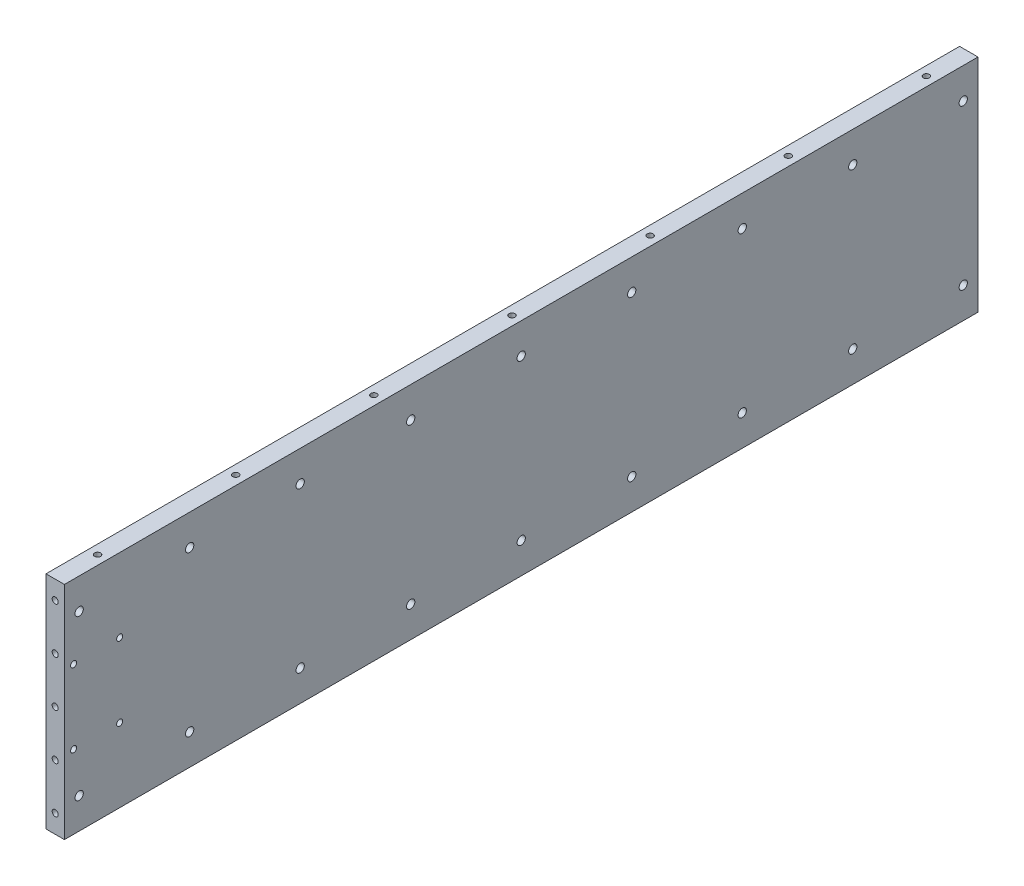
SolidWorks part; units mm, degrees
ref_plane "Front Plane" through (0, 0, 0) normal (0, 0, 1) x (1, 0, 0)
ref_plane "Top Plane" through (0, 0, 0) normal (0, 1, 0) x (1, 0, 0)
ref_plane "Right Plane" through (0, 0, 0) normal (1, 0, 0) x (0, 0, -1)
sketch "Sketch2" plane through (0, 0, 0) normal (0, 0, 1) x (1, 0, 0)
  line L0 (-10, 0) -> (0, 0)
  line L3 (0, 0) -> (0, -120)
  line L4 (0, -120) -> (-10, -120)
  line L5 (-10, -120) -> (-10, 0)
  dimension "D1" = 120
  dimension "D2" = 10
extrude "Boss-Extrude1" add sketch "Sketch2" along normal blind 496
sketch "Sketch3" plane through (0, 0, 496) normal (0, 0, 1) x (1, 0, 0)
  line L0 (-5, 0) -> (-5, -120) construction
  line L1 (0, 0) -> (-10, 0) construction
  line L2 (-10, -120) -> (0, -120) construction
  line L3 (-10, -60) -> (0, -60) construction
  line L4 (-10, 0) -> (-10, -120) construction
  line L5 (0, -120) -> (0, 0) construction
  point P12 (-5, -60)
  point P13 (-5, -110)
  point P14 (-5, -35)
  point P15 (-5, -10)
  point P16 (-5, -85)
  dimension "D1" = 3
hole_wizard "M4 Tapped Hole1" positions "3DSketch1" profile "Sketch4" tap size "M4" standard "ISO"
sketch3d "3DSketch1"
  point P0 (-5, -10, 496)
  point P3 (-5, -35, 496)
  point P6 (-5, -60, 496)
  point P9 (-5, -85, 496)
  point P12 (-5, -110, 496)
sketch "Sketch4" plane through (-5, -10, 496) normal (1, 0, 0) x (0, -1, 0)
  line L0 (0, 0) -> (0, 15.0914)
  line L1 (0, 15.0914) -> (1.65, 14.1)
  line L2 (1.65, 14.1) -> (1.65, 0)
  line L5 (1.65, 0) -> (0, 0)
  line L10 (0, 15.0914) -> (-1.65, 14.1) construction
  line L11 (0, -6.35) -> (0, 107.95) construction
  dimension "Tap Drill Dia." = 3.3
  dimension "Tap Drill Depth" = 14.1
  dimension "Drill Angle" = 118
sketch "Sketch5" plane through (0, 0, 0) normal (0, 0, -1) x (-1, 0, 0)
  line L0 (5, 0) -> (5, -120) construction
  line L1 (0, 0) -> (10, 0) construction
  line L2 (10, -120) -> (0, -120) construction
  line L3 (10, -60) -> (0, -60) construction
  point P10 (5, -60)
  point P11 (5, -85)
  point P12 (5, -35)
  point P13 (5, -10)
  point P14 (5, -110)
  dimension "D1" = 3
hole_wizard "M4 Tapped Hole2" positions "3DSketch2" profile "Sketch6" tap size "M4" standard "ISO"
sketch3d "3DSketch2"
  point P0 (-5, -10, 0)
  point P3 (-5, -35, 0)
  point P6 (-5, -60, 0)
  point P9 (-5, -85, 0)
  point P12 (-5, -110, 0)
sketch "Sketch6" plane through (-5, -10, 0) normal (1, 0, 0) x (0, 1, 0)
  line L0 (0, 0) -> (0, 15.0914)
  line L1 (0, 15.0914) -> (1.65, 14.1)
  line L2 (1.65, 14.1) -> (1.65, 0)
  line L5 (1.65, 0) -> (0, 0)
  line L10 (0, 15.0914) -> (-1.65, 14.1) construction
  line L11 (0, -6.35) -> (0, 107.95) construction
  dimension "Tap Drill Dia." = 3.3
  dimension "Tap Drill Depth" = 14.1
  dimension "Drill Angle" = 118
sketch "Sketch7" plane through (0, 0, 0) normal (1, 0, 0) x (0, 0, -1)
  line L0 (-496, -60) -> (0, -60) construction
  line L1 (0, 0) -> (0, -120) construction
  line L2 (-496, -16.7) -> (0, -16.7) construction
  line L3 (-496, 0) -> (-496, -120) construction
  line L4 (-496, 0) -> (0, 0) construction
  point P11 (-488, -16.7)
  point P12 (-8, -103.3)
  point P13 (-428, -16.7)
  point P14 (-368, -16.7)
  point P15 (-308, -16.7)
  point P16 (-248, -16.7)
  point P17 (-188, -16.7)
  point P18 (-128, -16.7)
  point P19 (-68, -16.7)
  point P20 (-8, -16.7)
  point P21 (-68, -103.3)
  point P22 (-128, -103.3)
  point P23 (-188, -103.3)
  point P24 (-248, -103.3)
  point P25 (-308, -103.3)
  point P26 (-368, -103.3)
  point P27 (-428, -103.3)
  point P28 (-488, -103.3)
  dimension "D1" = 16.7
  dimension "D2" = 8
  dimension "D3" = 9
hole_wizard "Ø4.5 (4.5) Diameter Hole1" positions "3DSketch3" profile "Sketch8" hole size "Ø4.5" standard "ISO" end condition through all
sketch3d "3DSketch3"
  point P0 (0, -16.7, 488)
  point P3 (0, -16.7, 428)
  point P6 (0, -16.7, 368)
  point P9 (0, -16.7, 308)
  point P12 (0, -16.7, 248)
  point P15 (0, -16.7, 188)
  point P18 (0, -16.7, 128)
  point P21 (0, -16.7, 68)
  point P24 (0, -16.7, 8)
  point P27 (0, -103.3, 8)
  point P30 (0, -103.3, 68)
  point P33 (0, -103.3, 128)
  point P36 (0, -103.3, 188)
  point P39 (0, -103.3, 248)
  point P42 (0, -103.3, 308)
  point P45 (0, -103.3, 368)
  point P48 (0, -103.3, 428)
  point P51 (0, -103.3, 488)
sketch "Sketch8" plane through (0, -16.7, 488) normal (0, 1, 0) x (0, 0, -1)
  line L0 (0, 0) -> (0, 10)
  line L1 (0, 10) -> (2.25, 10)
  line L2 (2.25, 10) -> (2.25, 0)
  line L5 (2.25, 0) -> (0, 0)
  line L11 (0, -6.35) -> (0, 107.95) construction
  dimension "Thru Hole Dia." = 4.5
  dimension "Thru Hole Depth" = 10
sketch "Sketch9" plane through (0, 0, 0) normal (1, 0, 0) x (0, 0, -1)
  line L0 (-495.4373, -40) -> (-462.5242, -40) construction
  line L1 (-504.5233, -37.9) -> (-462.0233, -37.9) construction
  line L2 (-504.5233, -42.1) -> (-462.0233, -42.1) construction
  line L4 (-462.5242, -80) -> (-495.4373, -80) construction
  line L5 (-504.5233, -77.9) -> (-462.0233, -77.9) construction
  line L6 (-504.5233, -82.1) -> (-462.0233, -82.1) construction
  line L7 (-496, -258) -> (-496, 0) construction
  line L10 (-496, 0) -> (-496, -120) construction
  point P12 (-466, -40)
  point P13 (-491, -40)
  point P18 (-491, -80)
  point P19 (-466, -80)
  dimension "D1" = 5
  dimension "D2" = 30
hole_wizard "M4 Tapped Hole3" positions "3DSketch5" profile "Sketch11" tap size "M4" standard "ISO" end condition through all
sketch3d "3DSketch5"
  point P0 (0, -40, 491)
  point P3 (0, -40, 466)
  point P6 (0, -80, 491)
  point P9 (0, -80, 466)
sketch "Sketch11" plane through (0, -40, 491) normal (0, 1, 0) x (0, 0, -1)
  line L0 (0, 0) -> (0, 10)
  line L1 (0, 10) -> (1.65, 10)
  line L2 (1.65, 10) -> (1.65, 0)
  line L5 (1.65, 0) -> (0, 0)
  line L11 (0, -6.35) -> (0, 107.95) construction
  dimension "Thread Major Dia." = 3.3
  dimension "Thru Tap Drill Depth" = 10
sketch "Sketch12" plane through (0, 0, 0) normal (0, 1, 0) x (1, 0, 0)
  point P0 (-5, -23)
  point P1 (-5, -98)
  point P3 (-5, -173)
  point P5 (-5, -248)
  point P7 (-5, -323)
  point P9 (-5, -398)
  point P16 (-5, -473)
hole_wizard "M4 Tapped Hole4" positions "3DSketch6" profile "Sketch13" tap size "M4" standard "ISO"
sketch3d "3DSketch6"
  line L0 (-5, 5, 23) -> (-5, 0, 23) construction
  line L1 (-5, 5, 98) -> (-5, 0, 98) construction
  line L2 (-5, 5, 173) -> (-5, 0, 173) construction
  line L3 (-5, 5, 248) -> (-5, 0, 248) construction
  line L4 (-5, 5, 323) -> (-5, 0, 323) construction
  line L5 (-5, 5, 398) -> (-5, 0, 398) construction
  line L6 (-5, 5, 473) -> (-5, 0, 473) construction
  point P0 (-5, 5, 23)
  point P4 (-5, 5, 98)
  point P8 (-5, 5, 173)
  point P12 (-5, 5, 248)
  point P16 (-5, 5, 323)
  point P20 (-5, 5, 398)
  point P24 (-5, 5, 473)
sketch "Sketch13" plane through (-5, 5, 23) normal (1, 0, 0) x (0, 0, 1)
  line L0 (0, 0) -> (0, 16.0914)
  line L1 (0, 16.0914) -> (1.65, 15.1)
  line L2 (1.65, 15.1) -> (1.65, 0)
  line L5 (1.65, 0) -> (0, 0)
  line L10 (0, 16.0914) -> (-1.65, 15.1) construction
  line L11 (0, -6.35) -> (0, 107.95) construction
  dimension "Tap Drill Dia." = 3.3
  dimension "Tap Drill Depth" = 15.1
  dimension "Drill Angle" = 118
